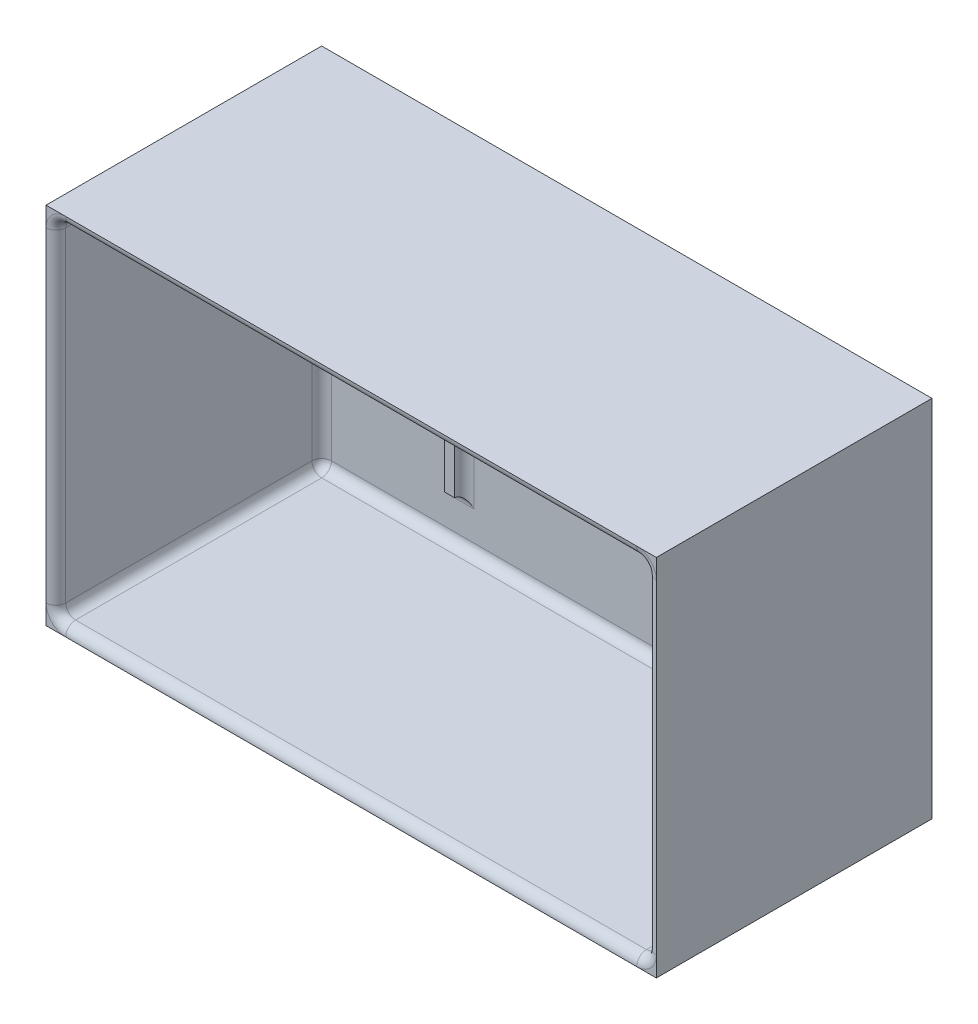
SolidWorks part; units mm, degrees
ref_plane "Plan de face" through (0, 0, 0) normal (0, 0, 1) x (1, 0, 0)
ref_plane "Plan de dessus" through (0, 0, 0) normal (0, 1, 0) x (1, 0, 0)
ref_plane "Plan de droite" through (0, 0, 0) normal (1, 0, 0) x (0, 0, -1)
sketch "Esquisse1" plane through (0, 0, 0) normal (0, 0, 1) x (1, 0, 0)
  line L1 (0, 0) -> (62, 0)
  line L2 (0, 0) -> (0, 37)
  line L3 (0, 37) -> (62, 37)
  line L4 (62, 0) -> (62, 37)
  dimension "D1" = 62
  dimension "D2" = 37
extrude "Boss.-Extru.1" add sketch "Esquisse1" along normal blind 28
shell "Coque1" thickness 1 removed face at (31, 18.5, 28)
fillet "Congé1" radius 1 12 edges at (31, 1, 28) (31, 36, 28) (61, 36, 14.5) (61, 18.5, 28) (61, 1, 14.5) (1, 1, 14.5) (1, 18.5, 28) (1, 36, 14.5) (31, 36, 1) (61, 18.5, 1) (31, 1, 1) (1, 18.5, 1)
sketch "Esquisse2" plane through (0, 0, 1) normal (0, 0, 1) x (1, 0, 0)
  line L0 (2, 2) -> (60, 2) construction
  line L1 (14.5, 31) -> (15.5, 31)
  line L2 (14.5, 31) -> (14.5, 6)
  line L3 (14.5, 6) -> (15.5, 6)
  line L4 (15.5, 31) -> (15.5, 6)
  line L5 (45.5, 31) -> (46.5, 31)
  line L6 (45.5, 31) -> (45.5, 6)
  line L7 (45.5, 6) -> (46.5, 6)
  line L8 (46.5, 31) -> (46.5, 6)
  line L9 (0, 35) -> (0, 2) construction
  dimension "D1" = 1
  dimension "D2" = 1
  dimension "D3" = 25
  dimension "D4" = 25
  dimension "D5" = 4
  dimension "D6" = 4
  dimension "D7" = 30
  dimension "D8" = 14.5
extrude "Boss.-Extru.2" add sketch "Esquisse2" along normal blind 1
fillet "Congé2" radius 1 8 edges at (46, 31, 1) (15, 31, 1) (46, 6, 1) (15, 6, 1) (46.5, 18.5, 1) (15.5, 18.5, 1) (45.5, 18.5, 1) (14.5, 18.5, 1)
